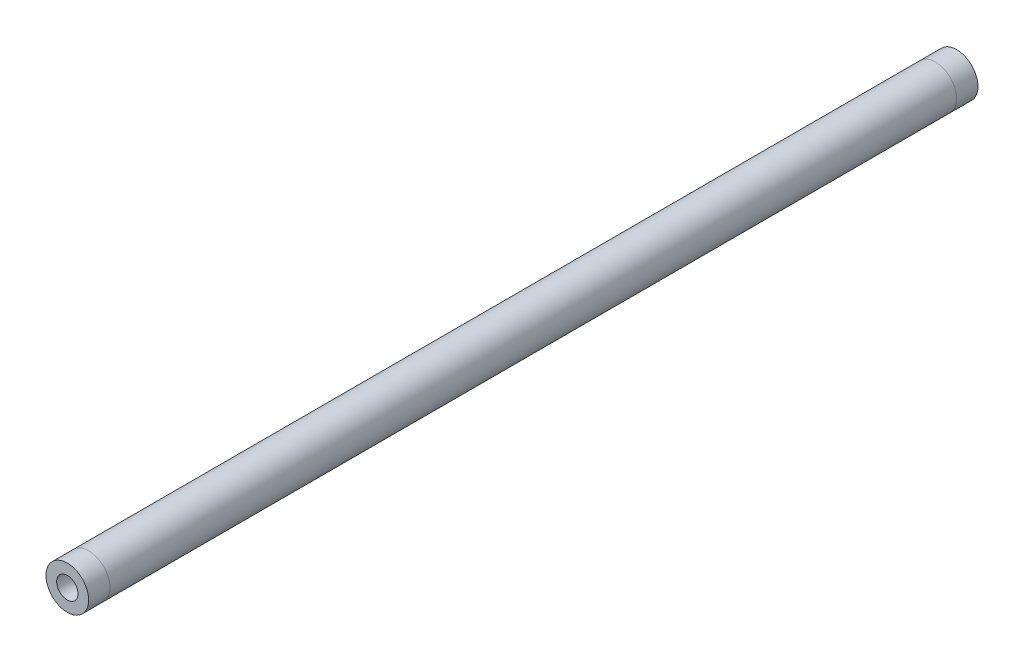
SolidWorks part; units mm, degrees
material "AISI 4130 Steel, annealed at 865C"
ref_plane "Front Plane" through (0, 0, 0) normal (0, 0, 1) x (1, 0, 0)
ref_plane "Top Plane" through (0, 0, 0) normal (0, 1, 0) x (1, 0, 0)
ref_plane "Right Plane" through (0, 0, 0) normal (1, 0, 0) x (0, 0, -1)
sketch "Axis" plane through (0, 0, 0) normal (1, 0, 0) x (0, 0, -1)
  line L0 (0, 0) -> (264.5736, 0) construction
  line L1 (264.5736, 0) -> (258.2236, 0)
  line L2 (264.5736, 0) -> (286.4684, 0) construction
  line L3 (0, 0) -> (-21.8948, 0) construction
  point P4 (0, 0)
  point P5 (264.5736, 0)
  point P6 (258.2236, 0)
  point P8 (286.4684, 0)
  dimension "D1" = 6.35
  dimension "D2" = 21.8948
  dimension "D3" = 21.8948
sketch "Sketch1" plane through (0, 0, 0) normal (0, 0, 1) x (1, 0, 0)
  circle A0 centre (0, 0) radius 6.35
  circle A1 centre (0, 0) radius 4.826
  circle A2 centre (0, 0) radius 3.175
  dimension "D1" = 12.7
  dimension "D2" = 1.524
  dimension "D3" = 6.35
extrude "Threaded insert 1-1" add sketch "Sketch1" against normal blind 6.35 contours A0 A1 | A1 A2 region at (-6.1704, 0, 0) region at (-4.6895, 0, 0)
extrude "Threaded insert 1-2" add sketch "Sketch1<3>" against normal blind 9.525 from surface contours A1 A2 region at (-4.6895, 0, 0) starting at face at (6.35, 0, -6.35)
sketch "Sketch1<3>" plane through (0, 0, 0) normal (0, 0, 1) x (1, 0, 0) same geometry as "Sketch1"
extrude "Tube extrude" add sketch "Sketch1<4>" against normal up to vertex (258.2236 mm away) from surface separate body contours A0 A1 region at (-6.1704, 0, 0) up to point (0, 0, -258.2236) starting at face at (4.826, 0, -6.35)
sketch "Sketch1<4>" plane through (0, 0, 0) normal (0, 0, 1) x (1, 0, 0) same geometry as "Sketch1"
extrude "Threaded insert 2-1" add sketch "Sketch1<6>" along normal blind 9.525 from surface separate body contours A1 A2 region at (-4.6895, 0, 0) starting at face at (4.826, 0, -258.2236)
sketch "Sketch1<6>" plane through (0, 0, 0) normal (0, 0, 1) x (1, 0, 0) same geometry as "Sketch1"
extrude "Threaded insert 2-2" add sketch "Sketch1<9>" against normal blind 6.35 from surface separate body contours A1 A2 | A0 A1 region at (-6.1704, 0, 0) region at (-4.6895, 0, 0) starting at face at (4.826, 0, -258.2236)
sketch "Sketch1<9>" plane through (0, 0, 0) normal (0, 0, 1) x (1, 0, 0) same geometry as "Sketch1"
combine bodies "Combine1" operation type add bodies to combine 106 104
equation "\"Threaded insert outer thickness\"= .25"
equation "\"D1@Threaded insert 1-1\"=\"Threaded insert outer thickness\""
equation "\"D1@Threaded insert 2-2\"=\"Threaded insert outer thickness\""
equation "\"D1@Axis\" = \"Threaded insert outer thickness\""
